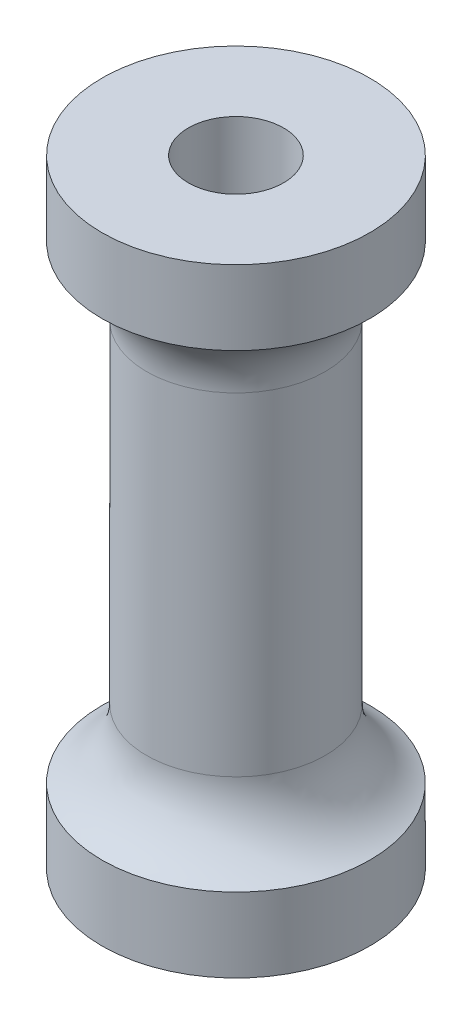
SolidWorks part; units mm, degrees
material "6061 Alloy"
ref_plane "Front Plane" through (0, 0, 0) normal (0, 0, 1) x (1, 0, 0)
ref_plane "Top Plane" through (0, 0, 0) normal (0, 1, 0) x (1, 0, 0)
ref_plane "Right Plane" through (0, 0, 0) normal (1, 0, 0) x (0, 0, -1)
sketch "Sketch1" plane through (0, 0, 0) normal (0, 1, 0) x (1, 0, 0)
  circle A0 centre (0, 0) radius 6
  circle A1 centre (0, 0) radius 3.2
  dimension "D1" = 12
  dimension "D2" = 6.4
extrude "Boss-Extrude1" add sketch "Sketch1" along normal blind 41.5
sketch "Sketch2" plane through (0, 0, 0) normal (0, 0, 1) x (1, 0, 0)
  line L0 (0, 42.2883) -> (0, -1.1758) construction
  line L1 (6, 41.5) -> (9, 41.5)
  line L2 (9, 41.5) -> (9, 36.5)
  line L3 (9, 36.5) -> (6, 36.5)
  line L4 (6, 0) -> (6, 41.5) construction
  line L5 (6, 36.5) -> (6, 41.5)
  line L6 (6, 0) -> (9, 0)
  line L7 (9, 0) -> (9, 5)
  line L8 (9, 5) -> (6, 5)
  line L9 (6, 5) -> (6, 0)
  dimension "D1" = 3
  dimension "D2" = 5
  dimension "D3" = 3
  dimension "D4" = 5
revolve "Revolve1" add sketch "Sketch2" angle 360 about L0
fillet "Fillet1" radius 5 2 edges at (0, 36.5, 6) (0, 5, -6)
